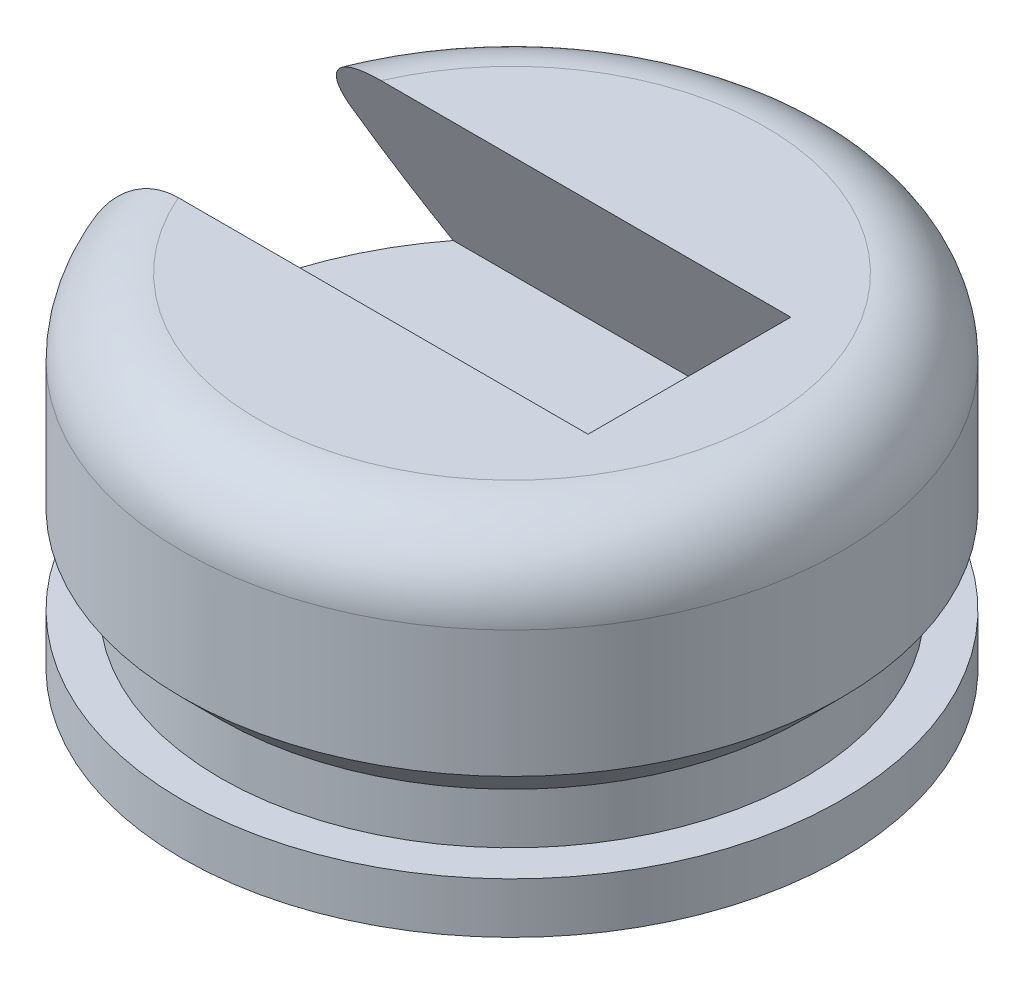
SolidWorks part; units mm, degrees
ref_plane "Front Plane" through (0, 0, 0) normal (0, 0, 1) x (1, 0, 0)
ref_plane "Top Plane" through (0, 0, 0) normal (0, 1, 0) x (1, 0, 0)
ref_plane "Side Plane" through (0, 0, 0) normal (1, 0, 0) x (0, 0, -1)
sketch "Sketch1" plane through (0, 0, 0) normal (0, 1, 0) x (1, 0, 0)
  circle A0 centre (0, 0) radius 13
  dimension "D1" = 26
extrude "Boss-Extrude1" add sketch "Sketch1" along normal blind 2
sketch "Sketch2" plane through (0, 2, 0) normal (0, 1, 0) x (1, 0, 0)
  circle A0 centre (0, 0) radius 11.5
  dimension "D1" = 23
extrude "Boss-Extrude2" add sketch "Sketch2" along normal blind 1.5
sketch "Sketch3" plane through (0, 3.5, 0) normal (0, 1, 0) x (1, 0, 0)
  circle A0 centre (0, 0) radius 13
  dimension "D1" = 26
extrude "Boss-Extrude4" add sketch "Sketch3" along normal blind 10
sketch "Sketch4" plane through (0, 0, 0) normal (1, 0, 0) x (0, 0, -1)
  line L1 (13, 13.5) -> (-13, 13.5) construction
  line L2 (-0.0409, 5.5) -> (-8.0409, 5.5)
  line L3 (-8.0409, 5.5) -> (-4, 13.5)
  line L4 (-4, 13.5) -> (0, 13.5)
  line L5 (-0.0409, 5.5) -> (7.9591, 5.5)
  line L6 (7.9591, 5.5) -> (4, 13.5)
  line L7 (4, 13.5) -> (0, 13.5)
  dimension "D1" = 16
  dimension "D2" = 8
  dimension "D3" = 4
  dimension "D4" = 8
  dimension "D5" = 8
extrude "Cut-Extrude1" cut sketch "Sketch4" against normal through all and the other way blind 7
chamfer "Chamfer1" distance 2 angle 45 1 edges at (0, 3.5, 13)
fillet "Fillet1" radius 3 1 edges at (13, 13.5, 0) tangent propagation no
